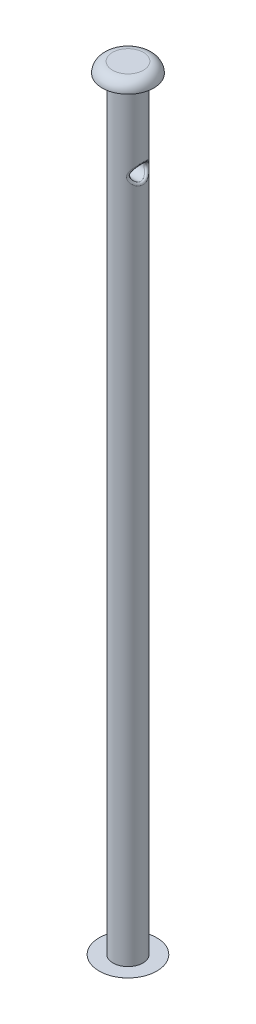
SolidWorks part; units mm, degrees
ref_plane "Front Plane" through (0, 0, 0) normal (0, 0, 1) x (1, 0, 0)
ref_plane "Top Plane" through (0, 0, 0) normal (0, 1, 0) x (1, 0, 0)
ref_plane "Right Plane" through (0, 0, 0) normal (1, 0, 0) x (0, 0, -1)
sketch "Sketch1" plane through (0, 0, 0) normal (0, 1, 0) x (1, 0, 0)
  circle A0 centre (0, 0) radius 3.683
  dimension "D1" = 7.366
extrude "Boss-Extrude1" add sketch "Sketch1" along normal blind 190.5
sketch "Sketch2" plane through (0, 0, 0) normal (1, 0, 0) x (0, 0, -1)
  line L0 (0, 0) -> (0, -3.81)
  line L1 (0, 0) -> (-7.112, 0)
  arc A0 (-7.112, 0) -> (0, -3.81) centre (9.2866, 22.0679) ccw
  dimension "D3" = 27.4938
  dimension "D1" = 7.112
  dimension "D2" = 3.81
revolve "Revolve1" add sketch "Sketch2" angle 360 about L0
sketch "Sketch3" plane through (0, 0, 0) normal (1, 0, 0) x (0, 0, -1)
  circle A0 centre (0, 168.402) radius 1.905
  point P5 (0, 0)
  dimension "D1" = 3.81
  dimension "D2" = 168.402
sketch "Sketch6" plane through (0, 190.5, 0) normal (0, 1, 0) x (1, 0, 0)
  circle A0 centre (0, 0) radius 6.35
  dimension "D1" = 12.7
extrude "Boss-Extrude4" add sketch "Sketch6" against normal blind 2.54
fillet "Fillet2" radius 2.54 1 edges at (0, 190.5, 6.35)
extrude "Cut-Extrude1" cut sketch "Sketch3" against normal through all both and the other way through all
fillet "Fillet3" radius 0.508 2 edges at (-3.1577, 168.2126, 1.8956) (3.1577, 168.5914, 1.8956)
